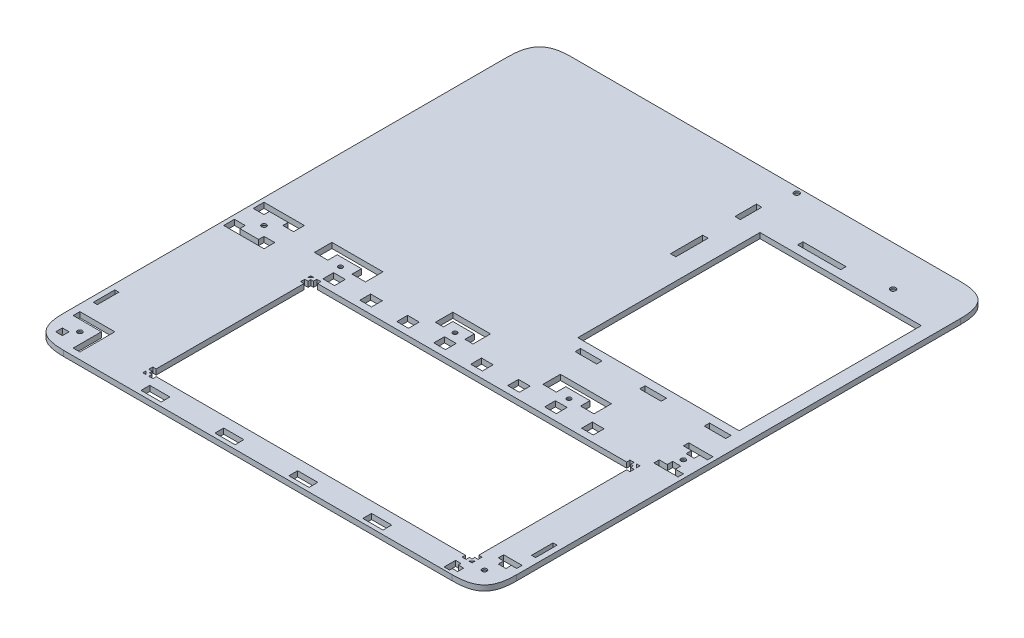
SolidWorks part; units mm, degrees
ref_plane "Front Plane" through (0, 0, 0) normal (0, 0, 1) x (1, 0, 0)
ref_plane "Top Plane" through (0, 0, 0) normal (0, 1, 0) x (1, 0, 0)
ref_plane "Right Plane" through (0, 0, 0) normal (1, 0, 0) x (0, 0, -1)
sketch "Sketch1" plane through (0, 0, 0) normal (0, 1, 0) x (1, 0, 0)
  line L1 (0, 0) -> (337, 0)
  line L2 (0, 0) -> (0, 377.97)
  line L3 (0, 377.97) -> (337, 377.97)
  line L4 (337, 0) -> (337, 377.97)
  line L5 (70.28, 137.5) -> (310.28, 137.5)
  line L6 (70.28, 137.5) -> (70.28, 17.5)
  line L7 (70.28, 17.5) -> (310.28, 17.5)
  line L8 (310.28, 137.5) -> (310.28, 17.5)
  dimension "D1" = 337
  dimension "D2" = 377.97
  dimension "D3" = 240
  dimension "D4" = 120
  dimension "D5" = 17.5
  dimension "D6" = 26.72
extrude "Boss-Extrude1" add sketch "Sketch1" against normal blind 4
fillet "Fillet1" radius 24 4 edges at (0, -2, 0) (337, -2, 0) (0, -2, -377.97) (337, -2, -377.97) conic rho 0.55
sketch "Sketch3" plane through (0, 0, 0) normal (0, 1, 0) x (1, 0, 0)
  line L0 (337, 24) -> (337, 353.97) construction
  line L1 (24, 0) -> (313, 0) construction
  line L2 (0, 353.97) -> (0, 24) construction
  line L3 (309, 4) -> (309, 2)
  line L4 (305, 10.5) -> (309, 10.5)
  line L5 (305, 10.5) -> (305, 2)
  line L6 (305, 2) -> (309, 2)
  line L7 (309, 10.5) -> (309, 8.5)
  line L8 (309, 8.5) -> (313, 8.5)
  line L10 (309, 4) -> (313, 4)
  line L11 (313, 8.5) -> (313, 4)
  line L12 (329, 28) -> (333, 28)
  line L13 (319.28, 32) -> (333, 32)
  line L14 (319.28, 32) -> (319.28, 28)
  line L15 (319.28, 28) -> (323.28, 28)
  line L16 (333, 32) -> (333, 28)
  line L18 (323.28, 28) -> (323.28, 24)
  line L19 (323.28, 24) -> (329, 24)
  line L20 (329, 28) -> (329, 24)
  line L21 (328, 151) -> (334, 151)
  line L30 (26, 5) -> (31, 5)
  line L36 (26, 5) -> (26, 26)
  line L37 (9, 14) -> (14, 14)
  line L38 (9, 14) -> (9, 9)
  line L39 (9, 9) -> (14, 9)
  line L40 (14, 14) -> (14, 9)
  line L41 (26, 31) -> (31, 31)
  line L42 (31, 5) -> (31, 31)
  line L43 (26, 31) -> (5, 31)
  line L45 (26, 26) -> (5, 26)
  line L46 (5, 31) -> (5, 26)
  line L47 (3, 140) -> (33, 140)
  line L48 (3, 140) -> (3, 144)
  line L49 (11, 144) -> (25, 144)
  line L50 (33, 140) -> (33, 144)
  line L52 (3, 144) -> (3, 148)
  line L53 (3, 148) -> (11, 148)
  line L54 (11, 144) -> (11, 148)
  line L56 (33, 144) -> (33, 148)
  line L57 (33, 148) -> (25, 148)
  line L58 (25, 144) -> (25, 148)
  line L59 (3, 170) -> (33, 170)
  line L60 (3, 170) -> (3, 166)
  line L61 (11, 166) -> (25, 166)
  line L62 (33, 170) -> (33, 166)
  line L64 (3, 166) -> (3, 162)
  line L65 (3, 162) -> (11, 162)
  line L66 (11, 166) -> (11, 162)
  line L68 (33, 166) -> (33, 162)
  line L69 (33, 162) -> (25, 162)
  line L70 (25, 166) -> (25, 162)
  line L71 (316, 147) -> (334, 147)
  line L72 (316, 147) -> (316, 151)
  line L73 (316, 151) -> (322, 151)
  line L74 (334, 147) -> (334, 151)
  line L76 (322, 151) -> (322, 155)
  line L77 (322, 155) -> (328, 155)
  line L78 (328, 151) -> (328, 155)
  line L79 (328, 169) -> (334, 169)
  line L80 (316, 173) -> (334, 173)
  line L81 (316, 173) -> (316, 169)
  line L82 (316, 169) -> (322, 169)
  line L83 (334, 173) -> (334, 169)
  line L85 (322, 169) -> (322, 165)
  line L86 (322, 165) -> (328, 165)
  line L87 (328, 169) -> (328, 165)
  line L88 (313, 377.97) -> (24, 377.97) construction
  line L89 (333, 42) -> (330, 42)
  line L90 (333, 42) -> (333, 58)
  line L91 (333, 58) -> (330, 58)
  line L92 (330, 42) -> (330, 58)
  line L93 (4, 42) -> (7, 42)
  line L94 (4, 42) -> (4, 58)
  line L95 (4, 58) -> (7, 58)
  line L96 (7, 42) -> (7, 58)
  line L97 (187.4, 351.97) -> (191.4, 351.97)
  line L98 (187.4, 351.97) -> (187.4, 335.97)
  line L99 (187.4, 335.97) -> (191.4, 335.97)
  line L100 (191.4, 351.97) -> (191.4, 335.97)
  line L102 (187.4, 311.97) -> (191.4, 311.97)
  line L103 (187.4, 311.97) -> (187.4, 287.97)
  line L104 (187.4, 287.97) -> (191.4, 287.97)
  line L105 (191.4, 311.97) -> (191.4, 287.97)
  line L106 (207, 334.97) -> (327, 334.97)
  line L107 (207, 334.97) -> (207, 199.47)
  line L108 (207, 199.47) -> (327, 199.47)
  line L109 (327, 334.97) -> (327, 199.47)
  line L110 (327, 193.47) -> (311, 193.47)
  line L111 (327, 193.47) -> (327, 189.47)
  line L112 (327, 189.47) -> (311, 189.47)
  line L113 (311, 193.47) -> (311, 189.47)
  line L114 (279, 193.47) -> (263, 193.47)
  line L115 (279, 193.47) -> (279, 189.47)
  line L116 (279, 189.47) -> (263, 189.47)
  line L117 (263, 193.47) -> (263, 189.47)
  line L118 (231, 193.47) -> (215, 193.47)
  line L119 (231, 193.47) -> (231, 189.47)
  line L120 (231, 189.47) -> (215, 189.47)
  line L121 (215, 193.47) -> (215, 189.47)
  line L122 (229, 344.97) -> (261, 344.97)
  line L123 (229, 344.97) -> (229, 340.97)
  line L124 (229, 340.97) -> (261, 340.97)
  line L125 (261, 344.97) -> (261, 340.97)
  circle A0 centre (322, 15) radius 1.75
  circle A1 centre (18, 18) radius 1.75
  circle A2 centre (18, 155) radius 1.75
  circle A3 centre (325, 160) radius 1.75
  circle A4 centre (195.4, 373.97) radius 2
  circle A5 centre (293, 347.97) radius 2
  point P37 (5, 28.5)
  dimension "D3" = 3.5
  dimension "D6" = 3.5
  dimension "D45" = 3.5
  dimension "D62" = 3.5
  dimension "D79" = 4
  dimension "D80" = 4
  dimension "D81" = 4
  dimension "D100" = 4
  dimension "D101" = 44
  dimension "D1" = 15
  dimension "D2" = 15
  dimension "D4" = 18
  dimension "D5" = 18
  dimension "D7" = 24
  dimension "D8" = 4
  dimension "D9" = 2
  dimension "D10" = 2
  dimension "D11" = 4.5
  dimension "D12" = 2
  dimension "D13" = 4
  dimension "D14" = 4
  dimension "D15" = 13.72
  dimension "D16" = 4
  dimension "D17" = 4
  dimension "D18" = 4
  dimension "D19" = 4
  dimension "D20" = 24
  dimension "D21" = 5
  dimension "D22" = 5
  dimension "D23" = 9
  dimension "D24" = 9
  dimension "D25" = 26
  dimension "D26" = 5
  dimension "D27" = 5
  dimension "D28" = 5
  dimension "D29" = 21
  dimension "D30" = 5
  dimension "D31" = 30
  dimension "D32" = 4
  dimension "D33" = 4
  dimension "D34" = 8
  dimension "D35" = 8
  dimension "D36" = 4
  dimension "D37" = 30
  dimension "D38" = 4
  dimension "D39" = 4
  dimension "D40" = 4
  dimension "D41" = 30
  dimension "D42" = 140
  dimension "D43" = 3
  dimension "D44" = 3
  dimension "D46" = 11
  dimension "D47" = 4
  dimension "D48" = 4
  dimension "D49" = 4
  dimension "D50" = 18
  dimension "D51" = 3
  dimension "D52" = 6
  dimension "D53" = 6
  dimension "D54" = 4
  dimension "D55" = 4
  dimension "D56" = 4
  dimension "D57" = 18
  dimension "D58" = 6
  dimension "D59" = 6
  dimension "D60" = 10
  dimension "D61" = 147
  dimension "D63" = 5
  dimension "D64" = 9
  dimension "D65" = 3
  dimension "D66" = 16
  dimension "D67" = 10
  dimension "D68" = 4
  dimension "D69" = 4
  dimension "D70" = 16
  dimension "D71" = 3
  dimension "D72" = 0
  dimension "D73" = 145.6
  dimension "D74" = 26
  dimension "D75" = 4
  dimension "D76" = 16
  dimension "D77" = 24
  dimension "D78" = 24
  dimension "D82" = 43
  dimension "D83" = 10
  dimension "D84" = 135.5
  dimension "D85" = 120
  dimension "D86" = 4
  dimension "D87" = 6
  dimension "D88" = 16
  dimension "D89" = 10
  dimension "D90" = 16
  dimension "D91" = 32
  dimension "D92" = 4
  dimension "D93" = 6
  dimension "D94" = 16
  dimension "D95" = 32
  dimension "D96" = 32
  dimension "D97" = 4
  dimension "D98" = 6
  dimension "D99" = 76
  dimension "D102" = 13
extrude "Cut-Extrude1" cut sketch "Sketch3" against normal up to next
ref_plane "Plane3" through (190.28, 0, 0) normal (-1, 0, 0) x (0, 0, 1)
ref_plane "Plane6" through (0, 0, -77.5) normal (0, 0, 1) x (1, 0, 0)
sketch "Sketch5" plane through (0, 0, 0) normal (0, 1, 0) x (1, 0, 0)
  line L0 (310.28, 17.5) -> (310.28, 137.5) construction
  line L3 (310.28, 15) -> (312.78, 15)
  line L4 (312.78, 17.5) -> (312.78, 15)
  line L5 (310.28, 22.5) -> (312.78, 22.5)
  line L6 (310.28, 22.5) -> (310.28, 19.5)
  line L7 (310.28, 19.5) -> (312.78, 19.5)
  line L8 (312.78, 22.5) -> (312.78, 19.5)
  line L9 (70.28, 17.5) -> (310.28, 17.5) construction
  line L10 (305.28, 17.5) -> (308.28, 17.5)
  line L11 (305.28, 17.5) -> (305.28, 15)
  line L12 (305.28, 15) -> (308.28, 15)
  line L13 (308.28, 17.5) -> (308.28, 15)
  line L14 (310.28, 15) -> (312.78, 17.5)
  dimension "D1" = 2.5
  dimension "D2" = 2.5
  dimension "D4" = 3
  dimension "D6" = 3
extrude "Cut-Extrude2" cut sketch "Sketch5" against normal up to next
mirror "Mirror1" about plane through (0, 0, -77.5) normal (0, 0, 1) of "Cut-Extrude2" second plane through (190.28, 0, 0) second plane normal (-1, 0, 0)
sketch "Sketch6" plane through (0, -4, 0) normal (0, -1, 0) x (1, 0, 0)
  circle A0 centre (18, -155) radius 3.5
  circle A1 centre (18, -18) radius 3.5
  circle A2 centre (322, -15) radius 3.5
  circle A3 centre (325, -160) radius 3.5
  circle A4 centre (195.4, -373.97) radius 3.5
  circle A5 centre (293, -347.97) radius 3.5
  dimension "D1" = 7
  dimension "D2" = 7
  dimension "D3" = 7
  dimension "D4" = 7
  dimension "D5" = 7
  dimension "D6" = 7
extrude "Cut-Extrude3" cut sketch "Sketch6" against normal blind 2.8
sketch "Sketch7" plane through (0, 0, 0) normal (0, 1, 0) x (1, 0, 0)
  line L0 (310.28, 22.5) -> (310.28, 132.5) construction
  line L1 (275.48, 142.5) -> (266.78, 142.5)
  line L2 (275.48, 142.5) -> (275.48, 150.5)
  line L3 (275.48, 150.5) -> (266.78, 150.5)
  line L4 (266.78, 142.5) -> (266.78, 150.5)
  line L5 (305.28, 137.5) -> (75.28, 137.5) construction
  dimension "D1" = 34.8
  dimension "D2" = 5
  dimension "D3" = 8.7
  dimension "D4" = 8
extrude "Cut-Extrude4" cut sketch "Sketch7" against normal up to next
pattern_linear "LPattern1" count 8 spacing 27.5 along (-1, 0, 0) of "Cut-Extrude4"
sketch "Sketch8" plane through (0, 0, 0) normal (0, 1, 0) x (1, 0, 0)
  line L0 (275.48, 150.5) -> (266.78, 150.5) construction
  line L1 (262.1, 156.38) -> (252.1, 156.38)
  line L2 (262.1, 156.38) -> (262.1, 163.38)
  line L4 (252.1, 156.38) -> (252.1, 163.38)
  line L5 (266.78, 150.5) -> (266.78, 142.5) construction
  line L7 (252.1, 163.38) -> (234.1, 163.38)
  line L8 (262.1, 163.38) -> (262.1, 169.38)
  line L9 (262.1, 169.38) -> (224.1, 169.38)
  line L10 (224.1, 163.38) -> (224.1, 169.38)
  line L12 (224.1, 163.38) -> (224.1, 156.38)
  line L13 (224.1, 156.38) -> (234.1, 156.38)
  line L14 (234.1, 163.38) -> (234.1, 156.38)
  dimension "D1" = 5.88
  dimension "D2" = 4.68
  dimension "D3" = 10
  dimension "D4" = 7
  dimension "D5" = 38
  dimension "D6" = 6
  dimension "D7" = 7
  dimension "D8" = 10
extrude "Cut-Extrude5" cut sketch "Sketch8" against normal up to next
ref_plane "Plane7" through (158.1, 0, 0) normal (1, 0, 0) x (0, 0, -1)
sketch "Sketch9" plane through (0, 0, 0) normal (0, 1, 0) x (1, 0, 0)
  line L0 (252.1, 163.38) -> (252.1, 156.38) construction
  line L1 (234.1, 163.38) -> (252.1, 163.38) construction
  circle A0 centre (243.1, 156.88) radius 1.6
  dimension "D1" = 9
  dimension "D2" = 6.5
  dimension "D3" = 3.2
extrude "Cut-Extrude6" cut sketch "Sketch9" against normal up to next
sketch "Sketch10" plane through (0, -4, 0) normal (0, -1, 0) x (1, 0, 0)
  circle A0 centre (243.1, -156.88) radius 3.5
  dimension "D1" = 7
extrude "Cut-Extrude7" cut sketch "Sketch10" against normal blind 2.8
mirror "Mirror2" about plane through (158.1, 0, 0) normal (1, 0, 0) of "Cut-Extrude6", "Cut-Extrude7", "Cut-Extrude5"
sketch "Sketch11" plane through (0, 0, 0) normal (0, 1, 0) x (1, 0, 0)
  line L0 (224.1, 169.38) -> (224.1, 156.38) construction
  line L1 (172.1, 169.38) -> (144.1, 169.38)
  line L2 (172.1, 169.38) -> (172.1, 163.38)
  line L3 (166.1, 163.38) -> (150.1, 163.38)
  line L4 (144.1, 169.38) -> (144.1, 163.38)
  line L5 (262.1, 169.38) -> (224.1, 169.38) construction
  line L6 (158.1, -2.2) -> (158.1, 2.2) construction
  line L7 (224.1, 156.38) -> (234.1, 156.38) construction
  line L9 (172.1, 163.38) -> (172.1, 156.38)
  line L10 (172.1, 156.38) -> (166.1, 156.38)
  line L11 (166.1, 163.38) -> (166.1, 156.38)
  line L13 (144.1, 163.38) -> (144.1, 156.38)
  line L14 (144.1, 156.38) -> (150.1, 156.38)
  line L15 (150.1, 163.38) -> (150.1, 156.38)
  circle A0 centre (158.1, 156.88) radius 1.6
  dimension "D9" = 6.5
  dimension "D10" = 3.2
  dimension "D1" = 28
  dimension "D2" = 52
  dimension "D3" = 0
  dimension "D4" = 6
  dimension "D5" = 6
  dimension "D6" = 6
  dimension "D7" = 0
  dimension "D8" = 0
extrude "Cut-Extrude8" cut sketch "Sketch11" against normal up to next
sketch "Sketch12" plane through (0, -4, 0) normal (0, -1, 0) x (1, 0, 0)
  circle A0 centre (158.1, -156.88) radius 3.5
  point P3 (0, 0)
extrude "Cut-Extrude9" cut sketch "Sketch12" against normal blind 2.8
sketch "Sketch13" plane through (0, 0, 0) normal (0, 1, 0) x (1, 0, 0)
  line L0 (70.28, 132.5) -> (70.28, 22.5) construction
  line L1 (78.5, 9.5) -> (93.5, 9.5)
  line L2 (78.5, 9.5) -> (78.5, 3)
  line L3 (78.5, 3) -> (93.5, 3)
  line L4 (93.5, 9.5) -> (93.5, 3)
  line L6 (24, 0) -> (313, 0) construction
  dimension "D1" = 8.22
  dimension "D2" = 3
  dimension "D3" = 15
  dimension "D4" = 6.5
extrude "Cut-Extrude10" cut sketch "Sketch13" against normal blind 4
pattern_linear "LPattern2" count 4 spacing 55 along (1, 0, 0) of "Cut-Extrude10"
